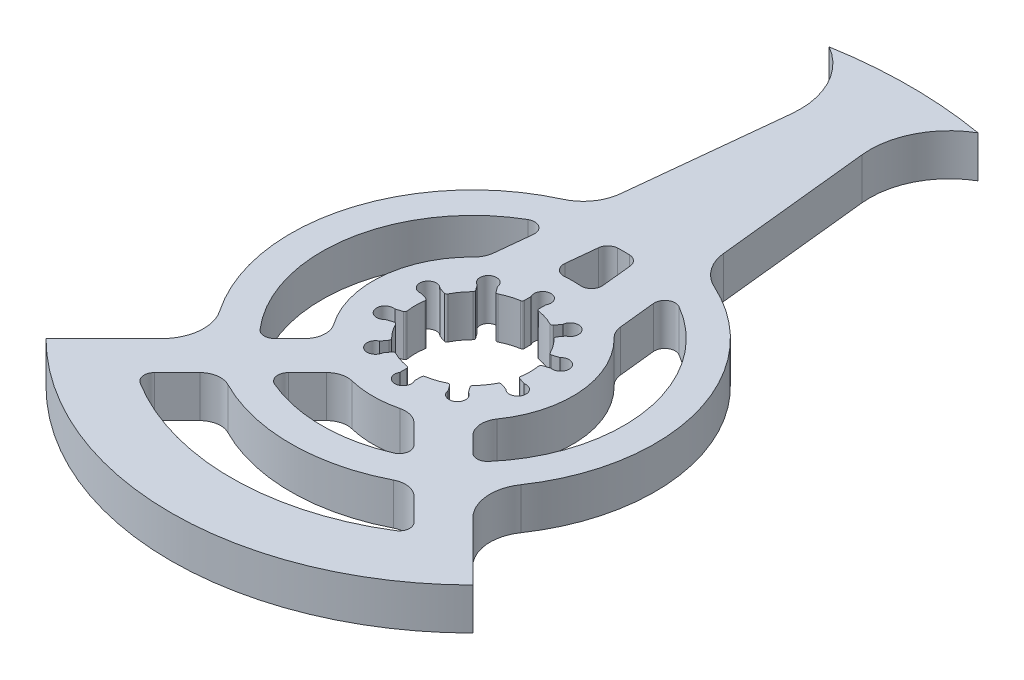
SolidWorks part; units mm, degrees
material "AISI Type A2 Tool Steel"
ref_plane "Front Plane" through (0, 0, 0) normal (0, 0, 1) x (1, 0, 0)
ref_plane "Top Plane" through (0, 0, 0) normal (0, 1, 0) x (1, 0, 0)
ref_plane "Right Plane" through (0, 0, 0) normal (1, 0, 0) x (0, 0, -1)
other "Center of Mass"
other "Bounding Box"
ref_plane "Default Plane" through (0, 2.286, 19.05) normal (0, -1, 0) x (-1, 0, 0)
sketch "Sketch1" plane through (0, 0, 0) normal (0, 1, 0) x (1, 0, 0)
  circle A0 centre (0, 0) radius 133.35 construction
  circle A1 centre (0, 0) radius 30.48
  circle A2 centre (0, 0) radius 17.4625
  dimension "D1" = 266.7
  dimension "D2" = 60.96
  dimension "D3" = 34.925
extrude "Boss-Extrude1" add sketch "Sketch1" along normal mid plane 12.7
sketch "Sketch2" plane through (0, 6.35, 0) normal (0, 1, 0) x (1, 0, 0)
  line L0 (-10.795, 107.95) -> (-19.6961, 23.2614)
  line L1 (19.6961, 23.2614) -> (10.795, 107.95)
  line L4 (0, 0) -> (0, 133.35) construction
  line L5 (-10.795, 107.95) -> (0, 107.95) construction
  line L6 (0, 107.95) -> (10.795, 107.95) construction
  line L7 (-22.6939, 131.4048) -> (0, 0) construction
  line L8 (-22.6939, 131.4048) -> (125.4677, 45.1673) construction
  circle A0 centre (0, 0) radius 133.35 construction
  circle A1 centre (0, 0) radius 133.35 construction
  arc A2 (-22.6939, 131.4048) -> (22.6939, 131.4048) centre (0, 0) cw
  arc A3 (-22.6939, 131.4048) -> (-10.795, 107.95) centre (-34.8727, 110.4807) cw
  circle A5 centre (0, 0) radius 30.48
  arc A6 (19.6961, 23.2614) -> (-19.6961, 23.2614) centre (0, 0) ccw
  arc A7 (-19.6961, 23.2614) -> (19.6961, 23.2614) centre (0, 0) ccw construction
  arc A8 (10.795, 107.95) -> (22.6939, 131.4048) centre (34.8727, 110.4807) cw
  dimension "D4" = 25.4
  dimension "D5" = 6
  dimension "D6" = 10.795
  dimension "D1" = 50
  dimension "D2" = 0
extrude "Boss-Extrude2" add sketch "Sketch2" against normal through all
sketch "Sketch3" plane through (0, 6.35, 0) normal (0, 1, 0) x (1, 0, 0)
  line L0 (-65.1069, -65.1069) -> (-21.5526, -21.5526)
  line L1 (21.5526, -21.5526) -> (65.1069, -65.1069)
  line L2 (0, -30.48) -> (0, -92.075) construction
  line L4 (-21.5526, -21.5526) -> (0, 0) construction
  line L5 (0, 0) -> (21.5526, -21.5526) construction
  arc A0 (-65.1069, -65.1069) -> (65.1069, -65.1069) centre (0, 0) ccw
  circle A1 centre (0, 0) radius 30.48 construction
  arc A3 (-21.5526, -21.5526) -> (21.5526, -21.5526) centre (0, 0) ccw
  point P13 (0, -92.075)
  dimension "D2" = 92.075
  dimension "D1" = 90
extrude "Boss-Extrude3" add sketch "Sketch3" against normal through all
sketch "Sketch5" plane through (0, 6.35, 0) normal (0, 1, 0) x (1, 0, 0)
  line L0 (0, 17.4625) -> (0, 21.2725) construction
  line L2 (-2.2225, 17.3205) -> (2.2225, 17.3205)
  line L3 (-2.2225, 17.3205) -> (-2.2225, 20.0168)
  line L5 (2.2225, 17.3205) -> (2.2225, 20.0168)
  arc A0 (2.2225, 20.0168) -> (-2.2225, 20.0168) centre (0, 21.2725) ccw
  circle A1 centre (0, 0) radius 17.4625 construction
  circle A2 centre (0, 21.2725) radius 4.5847 construction
  dimension "D2" = 5.1054
  dimension "D4" = 9.1694
  dimension "D1" = 3.81
  dimension "D3" = 4.445
extrude "Cut-Extrude2" cut sketch "Sketch5" against normal through all
pattern_circular "CirPattern1" count 10 over 360 about axis through (0, 6.35, 0) along (0, -1, 0) of "Cut-Extrude2"
sketch "Sketch6" plane through (0, 6.35, 0) normal (0, 1, 0) x (1, 0, 0)
  circle A0 centre (0, 0) radius 17.526
  arc A1 (-11.9788, 12.7062) -> (-15.786, 7.466) centre (0, 0) ccw construction
  dimension "D1" = 0.0635
extrude "Cut-Extrude3" cut sketch "Sketch6" against normal through all
sketch "Sketch7" plane through (0, 6.35, 0) normal (0, 1, 0) x (1, 0, 0)
  line L0 (-42.3252, -60.2857) -> (-10.6123, -28.5729)
  line L1 (10.6123, -28.5729) -> (42.3252, -60.2857)
  line L3 (-21.5526, -21.5526) -> (-65.1069, -65.1069) construction
  line L4 (65.1069, -65.1069) -> (21.5526, -21.5526) construction
  line L5 (-42.3252, -60.2857) -> (-51.3055, -51.3055) construction
  line L6 (42.3252, -60.2857) -> (51.3055, -51.3055) construction
  arc A0 (-10.6123, -28.5729) -> (10.6123, -28.5729) centre (0, 0) ccw
  arc A1 (-42.3252, -60.2857) -> (42.3252, -60.2857) centre (0, 0) ccw
  arc A2 (-65.1069, -65.1069) -> (65.1069, -65.1069) centre (0, 0) ccw construction
  arc A4 (21.5526, -21.5526) -> (19.6961, 23.2614) centre (0, 0) ccw construction
  dimension "D1" = 18.415
  dimension "D2" = 12.7
extrude "Cut-Extrude4" cut sketch "Sketch7" against normal through all
sketch "Sketch8" plane through (0, 6.35, 0) normal (0, 1, 0) x (1, 0, 0)
  circle A0 centre (0, 0) radius 46.0375
  circle A1 centre (0, 0) radius 55.5625
  dimension "D1" = 9.525
  dimension "D2" = 111.125
extrude "Boss-Extrude4" add sketch "Sketch8" against normal through all
sketch "Sketch11" plane through (0, 6.35, 0) normal (0, 1, 0) x (1, 0, 0)
  line L0 (-6.2352, 29.8354) -> (-4.5561, 45.8115)
  line L1 (4.5561, 45.8115) -> (6.2352, 29.8354)
  line L3 (-17.673, 42.5102) -> (-19.6961, 23.2614) construction
  line L4 (19.6961, 23.2614) -> (17.673, 42.5102) construction
  line L5 (-5.3956, 37.8235) -> (-18.0261, 39.151) construction
  line L6 (5.3956, 37.8235) -> (18.0261, 39.151) construction
  arc A0 (-6.2352, 29.8354) -> (6.2352, 29.8354) centre (0, 0) cw
  arc A1 (-4.5561, 45.8115) -> (4.5561, 45.8115) centre (0, 0) cw
  arc A2 (-19.6961, 23.2614) -> (-21.5526, -21.5526) centre (0, 0) ccw construction
  arc A3 (-17.673, 42.5102) -> (-32.5534, -32.5534) centre (0, 0) ccw construction
  dimension "D1" = 12.7
extrude "Cut-Extrude6" cut sketch "Sketch11" against normal through all
fillet "Fillet1" radius 6.35 8 edges at (-21.5526, 0, 21.5526) (21.5526, 0, 21.5526) (19.6961, 0, -23.2614) (-19.6961, 0, -23.2614) (10.6123, 0, 28.5729) (-10.6123, 0, 28.5729) (29.2683, 0, 47.2288) (-29.2683, 0, 47.2288)
fillet "Fillet6" radius 0.635 20 edges at (-12.0164, 0, -12.758) (-15.8469, 0, -7.4858) (-17.2204, 0, -3.2584) (-17.2204, 0, 3.2584) (-15.8469, 0, 7.4858) (-12.0164, 0, 12.758) (-8.4203, 0, 15.3707) (-2.2225, 0, 17.3845) (2.2225, 0, 17.3845) (8.4203, 0, 15.3707) (12.0164, 0, 12.758) (15.8469, 0, 7.4858) (17.2204, 0, 3.2584) (17.2204, 0, -3.2584) (15.8469, 0, -7.4858) (12.0164, 0, -12.758) (8.4203, 0, -15.3707) (2.2225, 0, -17.3845) (-2.2225, 0, -17.3845) (-8.4203, 0, -15.3707)
fillet "Fillet7" radius 3.175 12 edges at (-22.31, 0, 40.2705) (22.31, 0, 40.2705) (32.5534, 0, 32.5534) (-32.5534, 0, 32.5534) (-17.673, 0, -42.5102) (17.673, 0, -42.5102) (42.3252, 0, 60.2857) (-42.3252, 0, 60.2857) (-6.2352, 0, -29.8354) (6.2352, 0, -29.8354) (4.5561, 0, -45.8115) (-4.5561, 0, -45.8115)
fillet "Fillet8" radius 12.7 4 edges at (-16.5668, 0, -53.0352) (16.5668, 0, -53.0352) (39.2886, 0, 39.2886) (-39.2886, 0, 39.2886)
equation "\"Unit Measure\"= \"BoundingVolume\" / \"Thickness\"'in^2"
